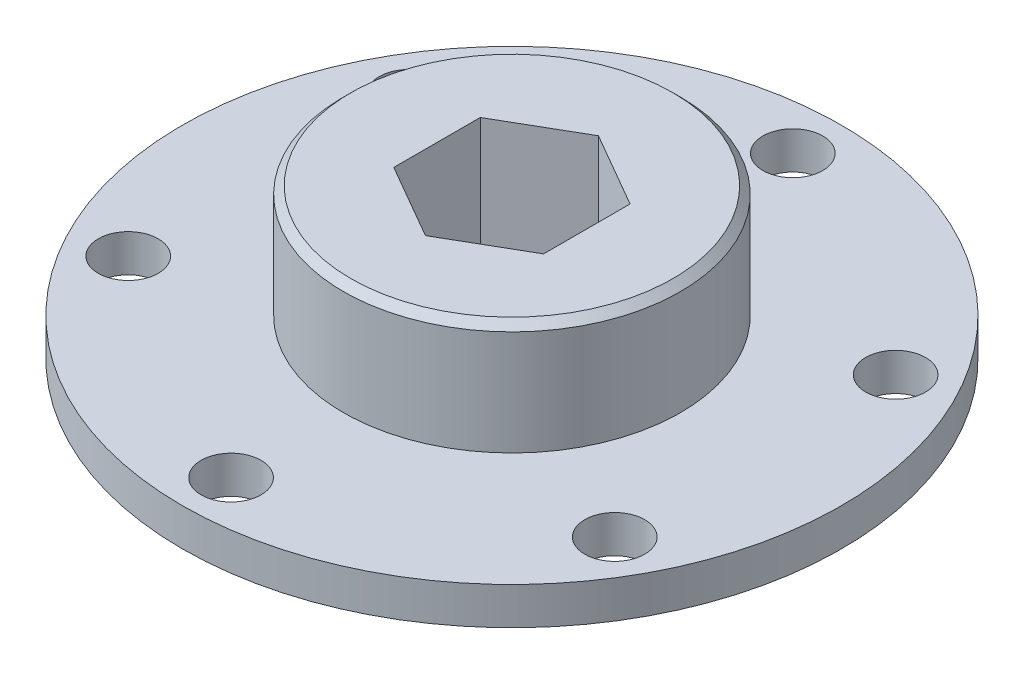
SolidWorks part; units mm, degrees
ref_plane "Front" through (0, 0, 0) normal (0, 0, 1) x (1, 0, 0)
ref_plane "Top" through (0, 0, 0) normal (0, 1, 0) x (1, 0, 0)
ref_plane "Right" through (0, 0, 0) normal (1, 0, 0) x (0, 0, -1)
sketch "Sketch1" plane through (0, 0, 0) normal (0, 1, 0) x (1, 0, 0)
  circle A0 centre (0, 0) radius 27.94
  dimension "D1" = 55.88
extrude "Boss-Extrude1" add sketch "Sketch1" along normal blind 3.175
sketch "Sketch2" plane through (0, 3.175, 0) normal (0, 1, 0) x (1, 0, 0)
  circle A0 centre (0, 0) radius 14.2875
  dimension "D1" = 28.575
extrude "Boss-Extrude2" add sketch "Sketch2" along normal blind 9.525
chamfer "Chamfer1" distance 0.635 angle 45 1 edges at (0, 12.7, 14.2875)
sketch "Sketch3" plane through (0, 12.7, 0) normal (0, 1, 0) x (1, 0, 0)
  line L0 (0, 0) -> (0, 7.3323) construction
  line L1 (6.35, 3.6662) -> (0, 7.3323)
  line L2 (0, 7.3323) -> (-6.35, 3.6662)
  line L3 (-6.35, 3.6662) -> (-6.35, -3.6662)
  line L4 (-6.35, -3.6662) -> (0, -7.3323)
  line L5 (0, -7.3323) -> (6.35, -3.6662)
  line L6 (6.35, -3.6662) -> (6.35, 3.6662)
  circle A0 centre (0, 0) radius 6.35 construction
extrude "Cut-Extrude2" cut sketch "Sketch3" against normal through all and the other way through all
sketch "Sketch4" plane through (0, 0, 0) normal (0, -1, 0) x (1, 0, 0)
  line L0 (0, 0) -> (0, 23.8125) construction
  circle A0 centre (0, 23.8125) radius 2.54
  circle A1 centre (20.6222, 11.9063) radius 2.54
  circle A2 centre (20.6222, -11.9062) radius 2.54
  circle A3 centre (0, -23.8125) radius 2.54
  circle A4 centre (-20.6222, -11.9063) radius 2.54
  circle A5 centre (-20.6222, 11.9062) radius 2.54
  point P17 (0, 0)
  dimension "D1" = 23.8125
  dimension "D3" = 5.08
  dimension "D2" = 6
extrude "Cut-Extrude3" cut sketch "Sketch4" against normal through all
